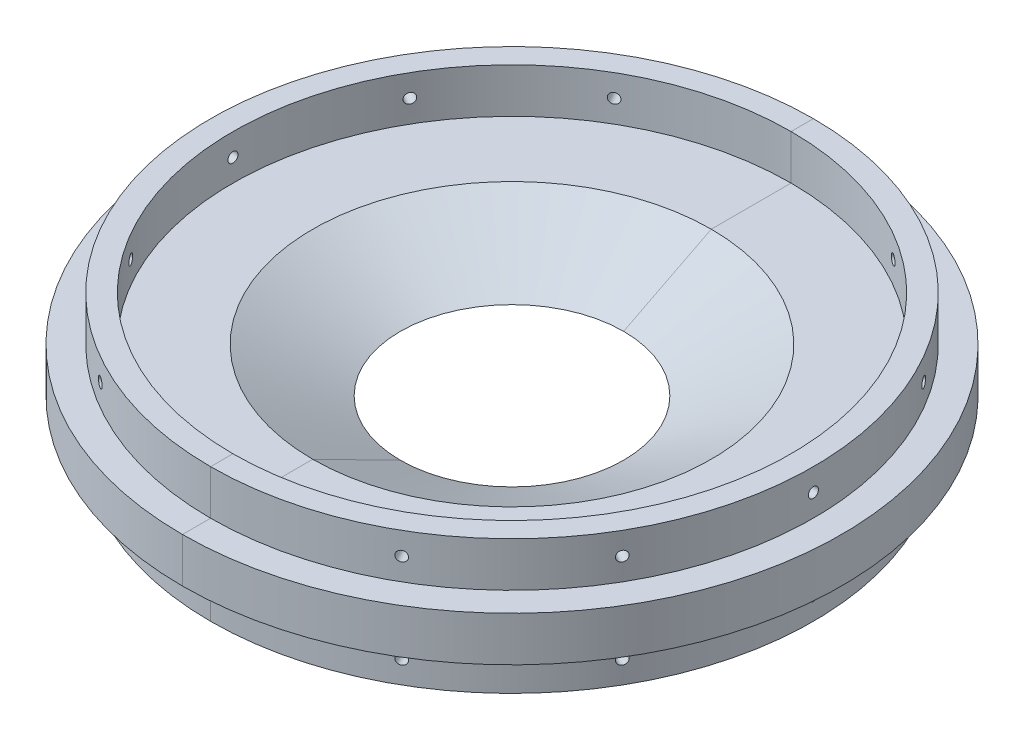
SolidWorks part; units mm, degrees
ref_plane "Front Plane" through (0, 0, 0) normal (0, 0, 1) x (1, 0, 0)
ref_plane "Top Plane" through (0, 0, 0) normal (0, 1, 0) x (1, 0, 0)
ref_plane "Right Plane" through (0, 0, 0) normal (1, 0, 0) x (0, 0, -1)
sketch "Sketch1" plane through (0, 0, 0) normal (0, 1, 0) x (1, 0, 0)
  circle A0 centre (0, 0) radius 93.726
  circle A1 centre (0, 0) radius 31.75
  dimension "D1" = 187.452
  dimension "D2" = 63.5
extrude "Boss-Extrude1" add sketch "Sketch1" along normal mid plane 12.7
sketch "Sketch5" plane through (0, 6.35, 0) normal (0, 1, 0) x (1, 0, 0)
  circle A0 centre (0, 0) radius 85.725
  circle A1 centre (0, 0) radius 79.375
  dimension "D1" = 171.45
  dimension "D2" = 158.75
extrude "Boss-Extrude2" add sketch "Sketch5" along normal blind 12.7
ref_plane "Plane1" through (0, 0, -85.725) normal (0, 0, -1) x (-1, 0, 0)
sketch "Sketch6" plane through (0, 0, -85.725) normal (0, 0, -1) x (-1, 0, 0)
  line L0 (0, 13.97) -> (0, -13.97) construction
  line L1 (93.726, 6.35) -> (-93.726, 6.35) construction
  circle A0 centre (0, 12.7) radius 1.4351
  dimension "D1" = 2.8702
  dimension "D2" = 6.35
extrude "Cut-Extrude1" cut sketch "Sketch6" against normal blind 12.7
pattern_circular "CirPattern1" count 12 over 360 about axis through (0, 6.35, 0) along (0, -1, 0) of "Cut-Extrude1" reverse direction yes
mirror "Mirror1" about plane through (0, 0, 0) normal (0, 1, 0) of "CirPattern1", "Cut-Extrude1", "Boss-Extrude2"
sketch "Sketch7" plane through (0, 19.05, 0) normal (0, 1, 0) x (1, 0, 0)
  line L0 (-25.7878, 75.0692) -> (-28.1663, 80.9657)
  line L1 (28.1663, 80.9657) -> (25.7878, 75.0692)
  arc A0 (28.1663, 80.9657) -> (-28.1663, 80.9657) centre (0, 0) ccw
  circle A1 centre (0, 0) radius 85.725 construction
  arc A2 (25.7878, 75.0692) -> (-25.7878, 75.0692) centre (0, 0) ccw
  circle A3 centre (0, 0) radius 79.375 construction
extrude "Boss-Extrude3" add sketch "Sketch7" against normal up to surface (12.7 mm away) up to face at (0, 6.35, 85.725)
mirror "Mirror3" about plane through (0, 0, 0) normal (0, 1, 0) of "Boss-Extrude3"
mirror "Mirror4" about plane through (0, 0, 0) normal (0, 0, 1) of "Boss-Extrude3"
mirror "Mirror5" about plane through (0, 0, 0) normal (0, 1, 0) of "Mirror4"
sketch "Sketch4" plane through (0, 0, 0) normal (0, 0, 1) x (1, 0, 0)
  line L0 (0, 23.2786) -> (0, -14.9525) construction
sketch "Sketch3" plane through (0, 0, 0) normal (0, 0, 1) x (1, 0, 0)
  line L0 (-31.75, -6.35) -> (-56.6752, 6.35)
  line L1 (93.726, 6.35) -> (-93.726, 6.35) construction
  line L2 (-56.6752, 6.35) -> (-31.75, 6.35)
  line L3 (-31.75, 6.35) -> (-31.75, -6.35)
  line L4 (-31.75, -6.35) -> (31.75, -6.35) construction
  line L5 (31.75, 6.35) -> (-31.75, 6.35) construction
  dimension "D1" = 27
revolve "Cut-Revolve1" cut sketch "Sketch3" angle 360 about L0
split "Split1" trim tools "Right Plane" bodies to split 103 resulting bodies 104 105
